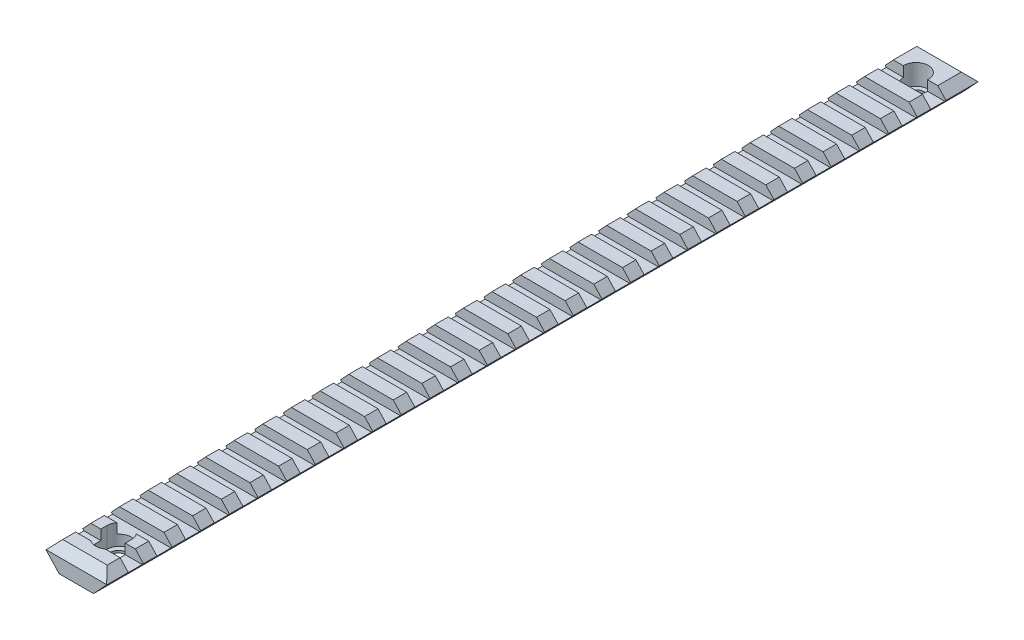
SolidWorks part; units mm, degrees
ref_plane "Front Plane" through (0, 0, 0) normal (0, 0, 1) x (1, 0, 0)
ref_plane "Top Plane" through (0, 0, 0) normal (0, 1, 0) x (1, 0, 0)
ref_plane "Right Plane" through (0, 0, 0) normal (1, 0, 0) x (0, 0, -1)
ref_plane "Plane1" through (0, 0, 304) normal (0, 0, 1) x (1, 0, 0)
sketch "Sketch1" plane through (0, 0, 304) normal (0, 0, 1) x (1, 0, 0)
  line L0 (-10.1906, 5.3792) -> (-7.75, 5.3792)
  line L1 (-7.75, 5.3792) -> (-7.75, 8)
  line L2 (-7.75, 8) -> (-10.1906, 5.3792)
extrude "Boss-Extrude1" add sketch "Sketch1" against normal blind 17.5
sketch "Sketch2" plane through (0, 5.3792, 0) normal (0, -1, 0) x (1, 0, 0)
  line L0 (-10.1906, 286.5) -> (-10.1906, 304)
  line L1 (-10.1906, 304) -> (-7.75, 304)
  line L2 (-7.75, 304) -> (-7.75, 286.5)
  line L3 (-7.75, 286.5) -> (-10.1906, 286.5)
extrude "Boss-Extrude2" add sketch "Sketch2" along normal blind 5.3792
sketch "Sketch3" plane through (0, 0, 286.5) normal (0, 0, -1) x (-1, 0, 0)
  line L0 (7.75, 8) -> (10.1906, 8)
  line L1 (10.1906, 8) -> (10.1906, 0)
  line L2 (10.1906, 0) -> (7.75, 0)
  line L3 (7.75, 0) -> (7.75, 8)
extrude "Boss-Extrude3" add sketch "Sketch3" along normal blind 286.5
sketch "Sketch4" plane through (-7.75, 0, 0) normal (1, 0, 0) x (0, 0, -1)
  line L0 (-304, 8) -> (0, 8)
  line L1 (0, 8) -> (0, 0)
  line L2 (0, 0) -> (-304, 0)
  line L3 (-304, 0) -> (-304, 8)
extrude "Boss-Extrude4" add sketch "Sketch4" along normal blind 17.9406
sketch "Sketch5" plane through (0, 0, 304) normal (0, 0, 1) x (1, 0, 0)
  line L0 (10.1906, 8) -> (7.75, 8)
  line L1 (7.75, 8) -> (10.1906, 5.3792)
  line L2 (10.1906, 5.3792) -> (10.1906, 8)
extrude "Cut-Extrude1" cut sketch "Sketch5" against normal blind 17.5
sketch "Sketch6" plane through (0, 8, 0) normal (0, 1, 0) x (-1, 0, 0)
  line L0 (10.1906, 286.5) -> (3.4, 286.5)
  line L1 (4.25, 289.05) -> (4.25, 304)
  line L2 (4.25, 304) -> (-4.25, 304)
  line L3 (-4.25, 304) -> (-4.25, 289.05)
  line L4 (-3.4, 286.5) -> (-10.1906, 286.5)
  line L5 (-10.1906, 286.5) -> (-10.1906, 0)
  line L6 (-10.1906, 0) -> (10.1906, 0)
  line L7 (10.1906, 0) -> (10.1906, 286.5)
  arc A0 (3.4, 286.5) -> (4.25, 289.05) centre (0, 289.05) ccw
  arc A1 (-4.25, 289.05) -> (-3.4, 286.5) centre (0, 289.05) ccw
extrude "Cut-Extrude2" cut sketch "Sketch6" against normal blind 2.6208
sketch "Sketch7" plane through (0, 5.3792, 0) normal (0, 1, 0) x (-1, 0, 0)
  line L0 (10.1906, 286.5) -> (3.4, 286.5)
  line L1 (4.25, 289.05) -> (4.25, 304)
  line L2 (4.25, 304) -> (-4.25, 304)
  line L3 (-4.25, 304) -> (-4.25, 289.05)
  line L4 (-3.4, 286.5) -> (-10.1906, 286.5)
  line L5 (-10.1906, 286.5) -> (-10.1906, 0)
  line L6 (-10.1906, 0) -> (10.1906, 0)
  line L7 (10.1906, 0) -> (10.1906, 286.5)
  arc A0 (3.4, 286.5) -> (4.25, 289.05) centre (0, 289.05) ccw
  arc A1 (-4.25, 289.05) -> (-3.4, 286.5) centre (0, 289.05) ccw
extrude "Cut-Extrude3" cut sketch "Sketch7" against normal blind 0.8792
sketch "Sketch8" plane through (0, 4.5, 0) normal (0, 1, 0) x (-1, 0, 0)
  line L0 (-4.25, 293.05) -> (-4.25, 289.05)
  line L1 (4.25, 289.05) -> (4.25, 293.05)
  arc A0 (4.25, 293.05) -> (-4.25, 293.05) centre (0, 293.05) ccw
  arc A1 (-4.25, 289.05) -> (4.25, 289.05) centre (0, 289.05) ccw
extrude "Cut-Extrude4" cut sketch "Sketch8" against normal blind 3.7
sketch "Sketch9" plane through (0, 0, 304) normal (0, 0, 1) x (1, 0, 0)
  line L0 (4.25, 8) -> (4.25, 4.5)
  line L1 (4.25, 4.5) -> (10.1906, 4.5)
  line L2 (10.1906, 4.5) -> (10.1906, 5.3792)
  line L3 (10.1906, 5.3792) -> (7.75, 8)
  line L4 (7.75, 8) -> (4.25, 8)
  line L5 (-4.25, 4.5) -> (-4.25, 8)
  line L6 (-4.25, 8) -> (-7.75, 8)
  line L7 (-7.75, 8) -> (-10.1906, 5.3792)
  line L8 (-10.1906, 5.3792) -> (-10.1906, 4.5)
  line L9 (-10.1906, 4.5) -> (-4.25, 4.5)
extrude "Cut-Extrude5" cut sketch "Sketch9" against normal blind 10.95
sketch "Sketch10" plane through (0, 0, 293.05) normal (0, 0, 1) x (1, 0, 0)
  line L0 (-4.25, 4.5) -> (-4.25, 8)
  line L1 (-4.25, 8) -> (-7.75, 8)
  line L2 (-7.75, 8) -> (-10.1906, 5.3792)
  line L3 (-10.1906, 5.3792) -> (-10.1906, 4.5)
  line L4 (-10.1906, 4.5) -> (-4.25, 4.5)
extrude "Cut-Extrude6" cut sketch "Sketch10" against normal blind 1.85
sketch "Sketch11" plane through (0, 0, 293.05) normal (0, 0, 1) x (1, 0, 0)
  line L0 (4.25, 8) -> (4.25, 4.5)
  line L1 (4.25, 4.5) -> (10.1906, 4.5)
  line L2 (10.1906, 4.5) -> (10.1906, 5.3792)
  line L3 (10.1906, 5.3792) -> (7.75, 8)
  line L4 (7.75, 8) -> (4.25, 8)
extrude "Cut-Extrude7" cut sketch "Sketch11" against normal blind 1.85
sketch "Sketch12" plane through (0, 4.5, 0) normal (0, 1, 0) x (-1, 0, 0)
  line L0 (-2.4819, 296.5) -> (-10.1906, 296.5)
  line L1 (-10.1906, 296.5) -> (-10.1906, 304)
  line L2 (-10.1906, 304) -> (10.1906, 304)
  line L3 (10.1906, 304) -> (10.1906, 296.5)
  line L4 (10.1906, 296.5) -> (2.4819, 296.5)
  arc A0 (2.4819, 296.5) -> (-2.4819, 296.5) centre (0, 293.05) ccw
extrude "Boss-Extrude5" add sketch "Sketch12" along normal blind 3.5
sketch "Sketch13" plane through (0, 4.5, 0) normal (0, 1, 0) x (-1, 0, 0)
  line L0 (10.1906, 0) -> (-10.1906, 0)
  line L1 (-10.1906, 0) -> (-10.1906, 281.2)
  line L2 (-10.1906, 281.2) -> (10.1906, 281.2)
  line L3 (10.1906, 281.2) -> (10.1906, 0)
extrude "Boss-Extrude6" add sketch "Sketch13" along normal blind 3.5
sketch "Sketch14" plane through (10.1906, 0, 0) normal (1, 0, 0) x (0, 0, -1)
  line L0 (-271.2, 8) -> (-276.5, 8)
  line L1 (-276.5, 8) -> (-276.5, 4.5)
  line L2 (-276.5, 4.5) -> (-271.2, 4.5)
  line L3 (-271.2, 4.5) -> (-271.2, 8)
extrude "Cut-Extrude8" cut sketch "Sketch14" against normal through all
sketch "Sketch15" plane through (10.1906, 0, 0) normal (1, 0, 0) x (0, 0, -1)
  line L0 (-261.2, 8) -> (-266.5, 8)
  line L1 (-266.5, 8) -> (-266.5, 4.5)
  line L2 (-266.5, 4.5) -> (-261.2, 4.5)
  line L3 (-261.2, 4.5) -> (-261.2, 8)
extrude "Cut-Extrude9" cut sketch "Sketch15" against normal through all
sketch "Sketch16" plane through (10.1906, 0, 0) normal (1, 0, 0) x (0, 0, -1)
  line L0 (-251.2, 8) -> (-256.5, 8)
  line L1 (-256.5, 8) -> (-256.5, 4.5)
  line L2 (-256.5, 4.5) -> (-251.2, 4.5)
  line L3 (-251.2, 4.5) -> (-251.2, 8)
extrude "Cut-Extrude10" cut sketch "Sketch16" against normal through all
sketch "Sketch17" plane through (10.1906, 0, 0) normal (1, 0, 0) x (0, 0, -1)
  line L0 (-241.2, 8) -> (-246.5, 8)
  line L1 (-246.5, 8) -> (-246.5, 4.5)
  line L2 (-246.5, 4.5) -> (-241.2, 4.5)
  line L3 (-241.2, 4.5) -> (-241.2, 8)
extrude "Cut-Extrude11" cut sketch "Sketch17" against normal through all
sketch "Sketch18" plane through (10.1906, 0, 0) normal (1, 0, 0) x (0, 0, -1)
  line L0 (-231.2, 8) -> (-236.5, 8)
  line L1 (-236.5, 8) -> (-236.5, 4.5)
  line L2 (-236.5, 4.5) -> (-231.2, 4.5)
  line L3 (-231.2, 4.5) -> (-231.2, 8)
extrude "Cut-Extrude12" cut sketch "Sketch18" against normal through all
sketch "Sketch19" plane through (10.1906, 0, 0) normal (1, 0, 0) x (0, 0, -1)
  line L0 (-221.2, 8) -> (-226.5, 8)
  line L1 (-226.5, 8) -> (-226.5, 4.5)
  line L2 (-226.5, 4.5) -> (-221.2, 4.5)
  line L3 (-221.2, 4.5) -> (-221.2, 8)
extrude "Cut-Extrude13" cut sketch "Sketch19" against normal through all
sketch "Sketch20" plane through (10.1906, 0, 0) normal (1, 0, 0) x (0, 0, -1)
  line L0 (-211.2, 8) -> (-216.5, 8)
  line L1 (-216.5, 8) -> (-216.5, 4.5)
  line L2 (-216.5, 4.5) -> (-211.2, 4.5)
  line L3 (-211.2, 4.5) -> (-211.2, 8)
extrude "Cut-Extrude14" cut sketch "Sketch20" against normal through all
sketch "Sketch21" plane through (10.1906, 0, 0) normal (1, 0, 0) x (0, 0, -1)
  line L0 (-201.2, 8) -> (-206.5, 8)
  line L1 (-206.5, 8) -> (-206.5, 4.5)
  line L2 (-206.5, 4.5) -> (-201.2, 4.5)
  line L3 (-201.2, 4.5) -> (-201.2, 8)
extrude "Cut-Extrude15" cut sketch "Sketch21" against normal through all
sketch "Sketch22" plane through (10.1906, 0, 0) normal (1, 0, 0) x (0, 0, -1)
  line L0 (-191.2, 8) -> (-196.5, 8)
  line L1 (-196.5, 8) -> (-196.5, 4.5)
  line L2 (-196.5, 4.5) -> (-191.2, 4.5)
  line L3 (-191.2, 4.5) -> (-191.2, 8)
extrude "Cut-Extrude16" cut sketch "Sketch22" against normal through all
sketch "Sketch23" plane through (10.1906, 0, 0) normal (1, 0, 0) x (0, 0, -1)
  line L0 (-181.2, 8) -> (-186.5, 8)
  line L1 (-186.5, 8) -> (-186.5, 4.5)
  line L2 (-186.5, 4.5) -> (-181.2, 4.5)
  line L3 (-181.2, 4.5) -> (-181.2, 8)
extrude "Cut-Extrude17" cut sketch "Sketch23" against normal through all
sketch "Sketch24" plane through (10.1906, 0, 0) normal (1, 0, 0) x (0, 0, -1)
  line L0 (-171.2, 8) -> (-176.5, 8)
  line L1 (-176.5, 8) -> (-176.5, 4.5)
  line L2 (-176.5, 4.5) -> (-171.2, 4.5)
  line L3 (-171.2, 4.5) -> (-171.2, 8)
extrude "Cut-Extrude18" cut sketch "Sketch24" against normal through all
sketch "Sketch25" plane through (10.1906, 0, 0) normal (1, 0, 0) x (0, 0, -1)
  line L0 (-161.2, 8) -> (-166.5, 8)
  line L1 (-166.5, 8) -> (-166.5, 4.5)
  line L2 (-166.5, 4.5) -> (-161.2, 4.5)
  line L3 (-161.2, 4.5) -> (-161.2, 8)
extrude "Cut-Extrude19" cut sketch "Sketch25" against normal through all
sketch "Sketch26" plane through (10.1906, 0, 0) normal (1, 0, 0) x (0, 0, -1)
  line L0 (-151.2, 8) -> (-156.5, 8)
  line L1 (-156.5, 8) -> (-156.5, 4.5)
  line L2 (-156.5, 4.5) -> (-151.2, 4.5)
  line L3 (-151.2, 4.5) -> (-151.2, 8)
extrude "Cut-Extrude20" cut sketch "Sketch26" against normal through all
sketch "Sketch27" plane through (10.1906, 0, 0) normal (1, 0, 0) x (0, 0, -1)
  line L0 (-141.2, 8) -> (-146.5, 8)
  line L1 (-146.5, 8) -> (-146.5, 4.5)
  line L2 (-146.5, 4.5) -> (-141.2, 4.5)
  line L3 (-141.2, 4.5) -> (-141.2, 8)
extrude "Cut-Extrude21" cut sketch "Sketch27" against normal through all
sketch "Sketch28" plane through (10.1906, 0, 0) normal (1, 0, 0) x (0, 0, -1)
  line L0 (-131.2, 8) -> (-136.5, 8)
  line L1 (-136.5, 8) -> (-136.5, 4.5)
  line L2 (-136.5, 4.5) -> (-131.2, 4.5)
  line L3 (-131.2, 4.5) -> (-131.2, 8)
extrude "Cut-Extrude22" cut sketch "Sketch28" against normal through all
sketch "Sketch29" plane through (10.1906, 0, 0) normal (1, 0, 0) x (0, 0, -1)
  line L0 (-121.2, 8) -> (-126.5, 8)
  line L1 (-126.5, 8) -> (-126.5, 4.5)
  line L2 (-126.5, 4.5) -> (-121.2, 4.5)
  line L3 (-121.2, 4.5) -> (-121.2, 8)
extrude "Cut-Extrude23" cut sketch "Sketch29" against normal through all
sketch "Sketch30" plane through (10.1906, 0, 0) normal (1, 0, 0) x (0, 0, -1)
  line L0 (-111.2, 8) -> (-116.5, 8)
  line L1 (-116.5, 8) -> (-116.5, 4.5)
  line L2 (-116.5, 4.5) -> (-111.2, 4.5)
  line L3 (-111.2, 4.5) -> (-111.2, 8)
extrude "Cut-Extrude24" cut sketch "Sketch30" against normal through all
sketch "Sketch31" plane through (10.1906, 0, 0) normal (1, 0, 0) x (0, 0, -1)
  line L0 (-101.2, 8) -> (-106.5, 8)
  line L1 (-106.5, 8) -> (-106.5, 4.5)
  line L2 (-106.5, 4.5) -> (-101.2, 4.5)
  line L3 (-101.2, 4.5) -> (-101.2, 8)
extrude "Cut-Extrude25" cut sketch "Sketch31" against normal through all
sketch "Sketch32" plane through (10.1906, 0, 0) normal (1, 0, 0) x (0, 0, -1)
  line L0 (-91.2, 8) -> (-96.5, 8)
  line L1 (-96.5, 8) -> (-96.5, 4.5)
  line L2 (-96.5, 4.5) -> (-91.2, 4.5)
  line L3 (-91.2, 4.5) -> (-91.2, 8)
extrude "Cut-Extrude26" cut sketch "Sketch32" against normal through all
sketch "Sketch33" plane through (10.1906, 0, 0) normal (1, 0, 0) x (0, 0, -1)
  line L0 (-81.2, 8) -> (-86.5, 8)
  line L1 (-86.5, 8) -> (-86.5, 4.5)
  line L2 (-86.5, 4.5) -> (-81.2, 4.5)
  line L3 (-81.2, 4.5) -> (-81.2, 8)
extrude "Cut-Extrude27" cut sketch "Sketch33" against normal through all
sketch "Sketch34" plane through (10.1906, 0, 0) normal (1, 0, 0) x (0, 0, -1)
  line L0 (-71.2, 8) -> (-76.5, 8)
  line L1 (-76.5, 8) -> (-76.5, 4.5)
  line L2 (-76.5, 4.5) -> (-71.2, 4.5)
  line L3 (-71.2, 4.5) -> (-71.2, 8)
extrude "Cut-Extrude28" cut sketch "Sketch34" against normal through all
sketch "Sketch35" plane through (10.1906, 0, 0) normal (1, 0, 0) x (0, 0, -1)
  line L0 (-61.2, 8) -> (-66.5, 8)
  line L1 (-66.5, 8) -> (-66.5, 4.5)
  line L2 (-66.5, 4.5) -> (-61.2, 4.5)
  line L3 (-61.2, 4.5) -> (-61.2, 8)
extrude "Cut-Extrude29" cut sketch "Sketch35" against normal through all
sketch "Sketch36" plane through (10.1906, 0, 0) normal (1, 0, 0) x (0, 0, -1)
  line L0 (-51.2, 8) -> (-56.5, 8)
  line L1 (-56.5, 8) -> (-56.5, 4.5)
  line L2 (-56.5, 4.5) -> (-51.2, 4.5)
  line L3 (-51.2, 4.5) -> (-51.2, 8)
extrude "Cut-Extrude30" cut sketch "Sketch36" against normal through all
sketch "Sketch37" plane through (10.1906, 0, 0) normal (1, 0, 0) x (0, 0, -1)
  line L0 (-41.2, 8) -> (-46.5, 8)
  line L1 (-46.5, 8) -> (-46.5, 4.5)
  line L2 (-46.5, 4.5) -> (-41.2, 4.5)
  line L3 (-41.2, 4.5) -> (-41.2, 8)
extrude "Cut-Extrude31" cut sketch "Sketch37" against normal through all
sketch "Sketch38" plane through (10.1906, 0, 0) normal (1, 0, 0) x (0, 0, -1)
  line L0 (-31.2, 8) -> (-36.5, 8)
  line L1 (-36.5, 8) -> (-36.5, 4.5)
  line L2 (-36.5, 4.5) -> (-31.2, 4.5)
  line L3 (-31.2, 4.5) -> (-31.2, 8)
extrude "Cut-Extrude32" cut sketch "Sketch38" against normal through all
sketch "Sketch39" plane through (10.1906, 0, 0) normal (1, 0, 0) x (0, 0, -1)
  line L0 (-21.2, 8) -> (-26.5, 8)
  line L1 (-26.5, 8) -> (-26.5, 4.5)
  line L2 (-26.5, 4.5) -> (-21.2, 4.5)
  line L3 (-21.2, 4.5) -> (-21.2, 8)
extrude "Cut-Extrude33" cut sketch "Sketch39" against normal through all
sketch "Sketch40" plane through (10.1906, 0, 0) normal (1, 0, 0) x (0, 0, -1)
  line L0 (-11.2, 8) -> (-16.5, 8)
  line L1 (-16.5, 8) -> (-16.5, 4.5)
  line L2 (-16.5, 4.5) -> (-11.2, 4.5)
  line L3 (-11.2, 4.5) -> (-11.2, 8)
extrude "Cut-Extrude34" cut sketch "Sketch40" against normal through all
sketch "Sketch41" plane through (0, 0.8, 0) normal (0, 1, 0) x (-1, 0, 0)
  line L0 (-2.75, 292.75) -> (-2.75, 289.35)
  line L1 (2.75, 289.35) -> (2.75, 292.75)
  arc A0 (-2.75, 289.35) -> (2.75, 289.35) centre (0, 289.35) ccw
  arc A1 (2.75, 292.75) -> (-2.75, 292.75) centre (0, 292.75) ccw
extrude "Cut-Extrude35" cut sketch "Sketch41" against normal through all
draft "Draft1" type of draft neutral plane draft angle 42.961 faces to draft 2 face at (10.1906, 6.1313, 153.7883) face at (-10.1906, 6.1313, 153.7883) neutral plane through (0, 4.5, 289.05) neutral plane normal (0, 1, 0) reverse direction yes parameters "D1"=42.961
hole_wizard "CBORE for #10 Binding Head Machine Screw1" positions "Sketch43" profile "Sketch42" counterbore size "#10" standard "ANSI Inch"
sketch "Sketch43" plane through (0, 8, 0) normal (0, 1, 0) x (1, 0, 0)
  point P0 (0, -11)
sketch "Sketch42" plane through (0, 8, 11) normal (1, 0, 0) x (0, 0, 1)
  line L0 (0, 0) -> (0, 8)
  line L1 (0, 8) -> (2.75, 8)
  line L3 (2.75, 8) -> (2.75, 7.2)
  line L4 (2.75, 7.2) -> (4.25, 7.2)
  line L5 (4.25, 7.2) -> (4.25, 0)
  line L7 (4.25, 0) -> (0, 0)
  line L11 (0, -6.35) -> (0, 107.95) construction
  dimension "Thru Hole Dia." = 5.5
  dimension "Thru Hole Depth" = 8
  dimension "C'Bore Dia." = 8.5
  dimension "C'Bore Depth" = 7.2
chamfer "Chamfer1" distance 4.1819 angle 85.922 29 edges at (13.45, 8, 258.85) (13.45, 8, 98.85) (13.45, 8, 178.85) (13.45, 8, 18.85) (13.45, 8, 218.85) (13.45, 8, 138.85) (13.45, 8, 58.85) (13.45, 8, 300.25) (13.45, 8, 238.85) (13.45, 8, 198.85) (13.45, 8, 158.85) (13.45, 8, 118.85) (13.45, 8, 78.85) (13.45, 8, 38.85) (13.45, 8, 268.85) (13.45, 8, 248.85) (13.45, 8, 228.85) (13.45, 8, 208.85) (13.45, 8, 188.85) (13.45, 8, 168.85) (13.45, 8, 148.85) (13.45, 8, 128.85) (13.45, 8, 108.85) (13.45, 8, 88.85) (13.45, 8, 68.85) (13.45, 8, 48.85) (13.45, 8, 28.85) (-13.45, 8, 5.6) (13.45, 8, 278.85) first distance on face at (11.703, 6.124, 153.7883) first distance on face at (-11.703, 6.124, 153.7883)
chamfer "Chamfer2" distance 3 angle 45 2 edges at (-2.85, 8, 304) (2.85, 8, 0)
chamfer "Chamfer3" distance 5.7 angle 47.039 29 edges at (-13.45, 8, 18.85) (-13.45, 8, 28.85) (-13.45, 8, 38.85) (-13.45, 8, 48.85) (-13.45, 8, 58.85) (-13.45, 8, 68.85) (-13.45, 8, 78.85) (-13.45, 8, 88.85) (-13.45, 8, 98.85) (-13.45, 8, 108.85) (-13.45, 8, 118.85) (-13.45, 8, 128.85) (-13.45, 8, 138.85) (-13.45, 8, 148.85) (-13.45, 8, 158.85) (-13.45, 8, 168.85) (-13.45, 8, 178.85) (-13.45, 8, 188.85) (-13.45, 8, 198.85) (-13.45, 8, 208.85) (-13.45, 8, 218.85) (-13.45, 8, 228.85) (-13.45, 8, 238.85) (-13.45, 8, 248.85) (-13.45, 8, 258.85) (-13.45, 8, 268.85) (13.45, 8, 7.1) (-13.45, 8, 278.85) (-13.45, 8, 298.75) first distance on face at (-2.85, 8, 18.85) first distance on face at (-2.85, 8, 28.85) first distance on face at (-2.85, 8, 38.85) first distance on face at (-2.85, 8, 48.85) first distance on face at (-2.85, 8, 58.85) first distance on face at (-2.85, 8, 68.85) first distance on face at (-2.85, 8, 78.85) first distance on face at (-2.85, 8, 88.85) first distance on face at (-2.85, 8, 98.85) first distance on face at (-2.85, 8, 108.85) first distance on face at (-2.85, 8, 118.85) first distance on face at (-2.85, 8, 128.85) first distance on face at (-2.85, 8, 138.85) first distance on face at (-2.85, 8, 148.85) first distance on face at (-2.85, 8, 158.85) first distance on face at (-2.85, 8, 168.85) first distance on face at (-2.85, 8, 178.85) first distance on face at (-2.85, 8, 188.85) first distance on face at (-2.85, 8, 198.85) first distance on face at (-2.85, 8, 208.85) first distance on face at (-2.85, 8, 218.85) first distance on face at (-2.85, 8, 228.85) first distance on face at (-2.85, 8, 238.85) first distance on face at (-2.85, 8, 248.85) first distance on face at (-2.85, 8, 258.85) first distance on face at (-2.85, 8, 268.85) first distance on face at (1.9, 8, 7.725) first distance on face at (-2.85, 8, 278.85) first distance on face at (-1.9, 8, 298.1333)
